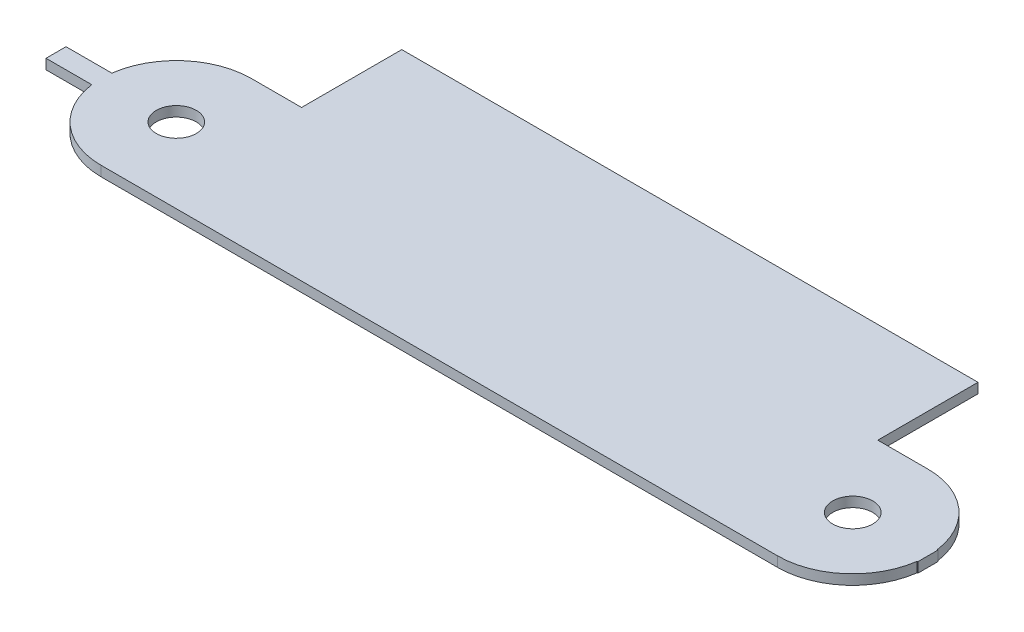
SolidWorks part; units mm, degrees
ref_plane "Front Plane" through (0, 0, 0) normal (0, 0, 1) x (1, 0, 0)
ref_plane "Top Plane" through (0, 0, 0) normal (0, 1, 0) x (1, 0, 0)
ref_plane "Right Plane" through (0, 0, 0) normal (1, 0, 0) x (0, 0, -1)
sketch "Sketch1" plane through (0, 0, 0) normal (0, 1, 0) x (1, 0, 0)
  line L0 (0, 0) -> (67.5, 0) construction
  line L1 (0, 7.5) -> (5, 7.5)
  line L2 (0, 7.5) -> (67.5, 7.5) construction
  line L3 (0, 7.5) -> (0, -7.5) construction
  line L4 (0, -7.5) -> (67.5, -7.5)
  line L5 (67.5, 7.5) -> (67.5, -7.5) construction
  line L6 (0, 7.5) -> (67.5, -7.5) construction
  line L7 (0, -7.5) -> (67.5, 7.5) construction
  line L8 (5, 7.5) -> (5, 17.5)
  line L9 (5, 17.5) -> (62.5, 17.5)
  line L10 (62.5, 17.5) -> (62.5, 7.5)
  line L11 (62.5, 7.5) -> (67.5, 7.5)
  line L12 (33.75, 0) -> (33.75, 17.5) construction
  line L13 (74.933, 1) -> (75, 1)
  line L14 (75, 1) -> (75, -1)
  line L15 (75, -1) -> (74.933, -1)
  line L17 (67.5, 0) -> (75, 0) construction
  line L31 (-7.5, 0) -> (-12.003, 0) construction
  line L32 (-12.003, 1) -> (-12.003, -1)
  line L33 (-12.003, -1) -> (-7.433, -1)
  line L44 (-12.003, 1) -> (-7.433, 1)
  circle A0 centre (0, 0) radius 2
  circle A1 centre (67.5, 0) radius 2
  arc A2 (0, 7.5) -> (0, -7.5) centre (0, 0) ccw construction
  arc A3 (67.5, -7.5) -> (67.5, 7.5) centre (67.5, 0) ccw construction
  arc A5 (67.5, 7.5) -> (74.933, 1) centre (67.5, 0) cw
  arc A7 (74.933, -1) -> (67.5, -7.5) centre (67.5, 0) cw
  arc A8 (-7.433, 1) -> (0, 7.5) centre (0, 0) cw
  arc A9 (-7.433, -1) -> (0, -7.5) centre (0, 0) ccw
  point P5 (33.75, 0)
  dimension "D3" = 10
  dimension "D6" = 4
  dimension "D8" = 87.003
  dimension "D2" = 15
  dimension "D4" = 75
  dimension "D5" = 5
  dimension "D7" = 2
  dimension "D12" = 4.57
  dimension "D13" = 2
extrude "Boss-Extrude1" add sketch "Sketch1" along normal blind 1 contours L4 A3 L11 L10 L9 L8 L1 A2 A0 A1 | L14 L9 | A3 | A2 L44 L32 L33 region at (33.5259, 0, -4.1114)
